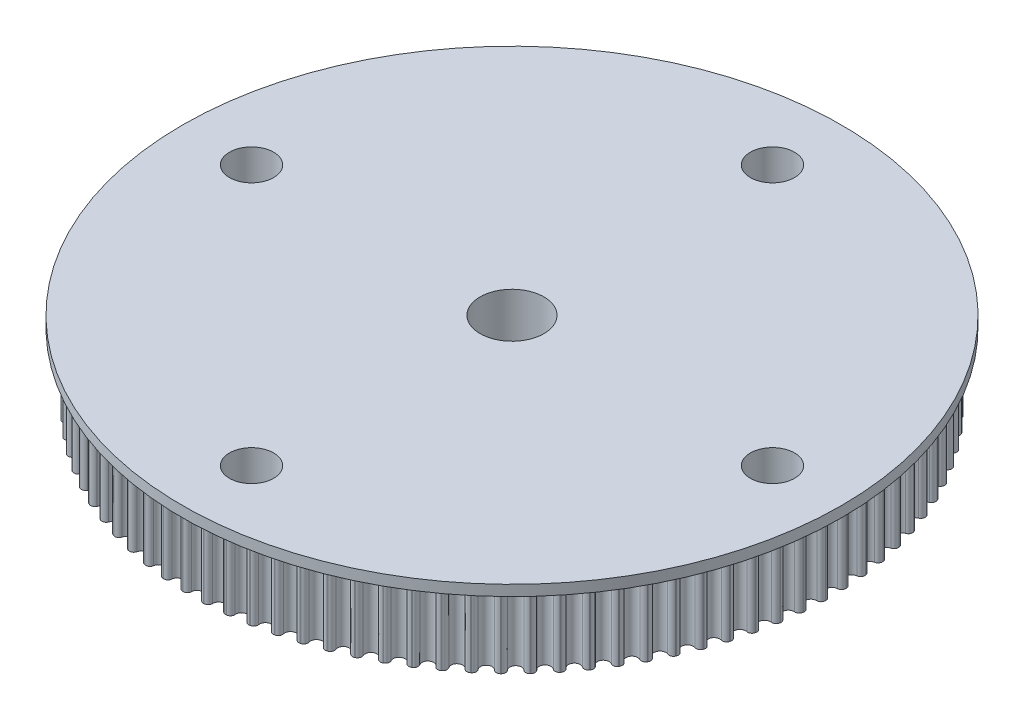
SolidWorks part; units mm, degrees
ref_plane "Front plan" through (0, 0, 0) normal (0, 0, 1) x (1, 0, 0)
ref_plane "Top plan" through (0, 0, 0) normal (0, 1, 0) x (1, 0, 0)
ref_plane "Right plan" through (0, 0, 0) normal (1, 0, 0) x (0, 0, -1)
sketch "Skica2" plane through (0, 0, 0) normal (0, 0, 1) x (1, 0, 0)
  line L0 (30, -3) -> (30, -4)
  line L1 (3, 4) -> (3, -4)
  line L3 (0, -9) -> (0, 9) construction
  line L7 (31, 3) -> (30, 3)
  line L8 (30, 3) -> (30, -3)
  line L9 (31, 3) -> (31, 4)
  line L12 (31, -4) -> (3.107, -4)
  line L13 (31, 4) -> (7.5, 4)
  line L14 (31, -4) -> (31, -3)
  line L15 (30, -3) -> (31, -3)
  line L17 (7.5, 4) -> (3, 4)
  line L18 (3.107, -4) -> (3, -4)
  point P3 (3, 0)
  point P7 (0, 0)
  dimension "D3" = 60
  dimension "D1" = 6
  dimension "D2" = 8
  dimension "D4" = 1
  dimension "D5" = 1
revolve "Revolute" add sketch "Skica2" angle 360 about L3 region at (16.5645, 0.0161, 0)
sketch "Sketch2" plane through (0, 3, 0) normal (0, -1, 0) x (1, 0, 0)
  line L0 (0, 0) -> (0, 29.6088) construction
  line L1 (0, 0) -> (10.1159, 28.243) construction
  line L3 (0, 0) -> (-2.5223, 29.8938) construction
  circle A1 centre (0, 0) radius 29.0588 construction
  circle A2 centre (0, 0) radius 29.6 construction
  arc A3 (-0.5498, 29.5949) -> (0.5498, 29.5949) centre (0, 29.6088) ccw
  arc A7 (-0.9625, 29.9846) -> (-2.5223, 29.8938) centre (0, 0) ccw
  arc A8 (0, 31.2377) -> (2.5223, 29.8938) centre (0.9517, 29.9849) cw
  circle A9 centre (0, 0) radius 30 construction
  arc A10 (0.9625, 29.9846) -> (2.5223, 29.8938) centre (0, 0) cw
  arc A11 (0.9625, 29.9846) -> (0.5498, 29.5949) centre (0.9497, 29.5848) ccw
  arc A12 (0, 31.2377) -> (-2.5223, 29.8938) centre (-0.9517, 29.9849) ccw
  arc A13 (-0.9625, 29.9846) -> (-0.5498, 29.5949) centre (-0.9497, 29.5848) cw
  dimension "D2" = 0.8
  dimension "D4" = 0.55
  dimension "D6" = 60
  dimension "D3" = 1.5733
  dimension "D1" = 0.4
extrude "Cut-Extrude3" cut sketch "Sketch2" along normal up to surface (7 mm away)
pattern_circular "CirPattern1" count 95 over 360 about axis through (0, -9, 0) along (0, -1, 0) of "Cut-Extrude3"
sketch "Sketch4" plane through (0, -4, 0) normal (0, -1, 0) x (1, 0, 0)
  circle A0 centre (0, 0) radius 20.125
  circle A1 centre (0, 0) radius 9.25
  dimension "D1" = 40.25
  dimension "D2" = 18.5
extrude "Cut-Extrude4" [suppressed] cut sketch "Sketch4" against normal blind 3.5
ref_plane "Plane1" through (0, 2.35, 0) normal (0, -1, 0) x (-1, 0, 0)
mirror "Mirror1" [suppressed] about plane through (0, 2.35, 0) normal (0, -1, 0)
sketch "Sketch7" plane through (0, -4, 0) normal (0, -1, 0) x (1, 0, 0)
  circle A0 centre (-24.5, 0) radius 2.075
  dimension "D1" = 4.15
  dimension "D2" = 24.5
extrude "Cut-Extrude5" cut sketch "Sketch7" against normal through all
pattern_circular "CirPattern2" count 4 over 270 about axis through (0, -4, 0) along (0, -1, 0) of "Cut-Extrude5"
sketch "Sketch8" [suppressed] plane through (0, -6.3, 0) normal (0, -1, 0) x (1, 0, 0)
  arc A0 (-0.686, 29.6969) -> (0.6524, 29.63) centre (0, 30) ccw
  circle A1 centre (0, 0) radius 30 construction
  arc A2 (-1.0508, 29.7419) -> (-1.0341, 30.3807) centre (1.3116, 30) cw
  dimension "D1" = 0.75
equation "\"`\"=2"
equation "\"D6@Sketch2\"= \"D3@Skica2\""
